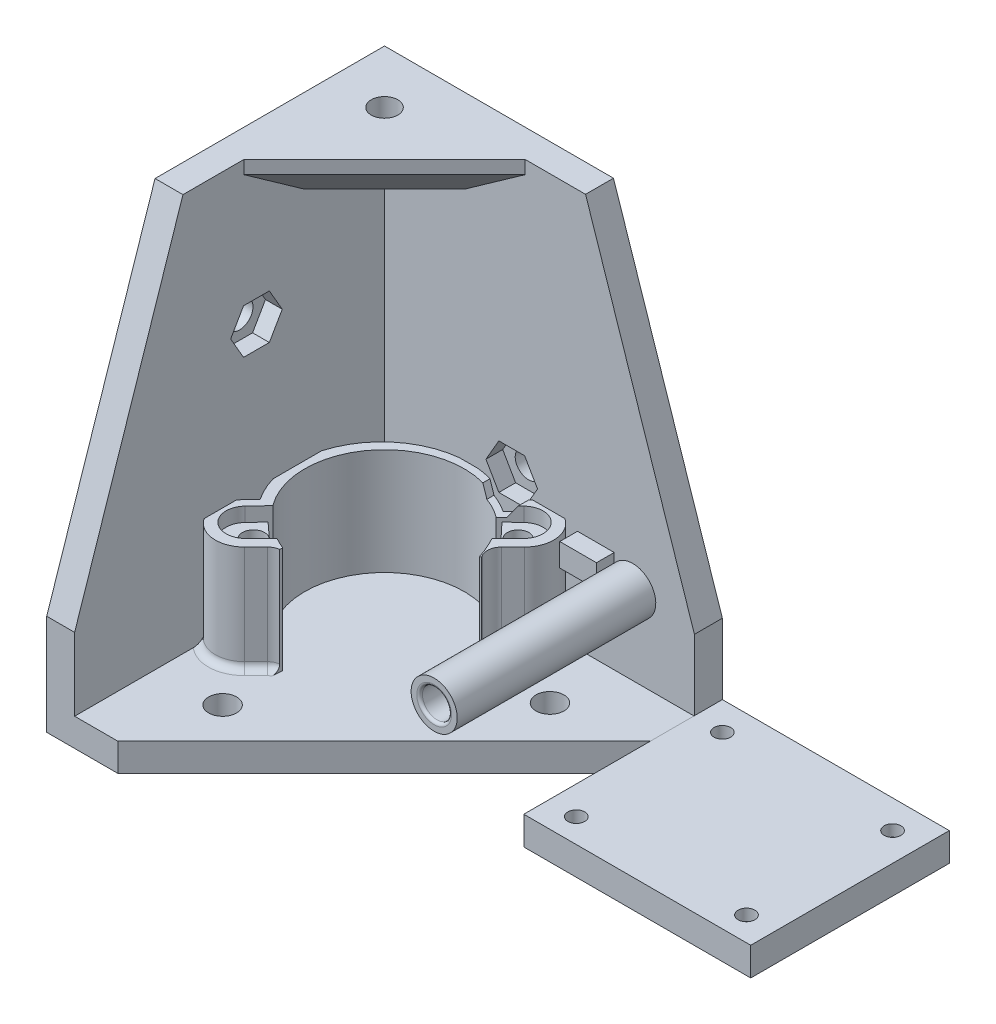
SolidWorks part; units mm, degrees
ref_plane "Front" through (0, 0, 0) normal (0, 0, 1) x (1, 0, 0)
ref_plane "Top" through (0, 0, 0) normal (0, 1, 0) x (1, 0, 0)
ref_plane "Right" through (0, 0, 0) normal (1, 0, 0) x (0, 0, -1)
sketch "Sketch1" plane through (0, 0, 0) normal (0, 1, 0) x (1, 0, 0)
  line L0 (0, 0) -> (0, 60.5)
  line L1 (0, -55) -> (0, 55) construction
  line L2 (0, 60.5) -> (60.5, 60.5)
  line L3 (60.5, 60.5) -> (60.5, 47.75)
  line L4 (60.5, 47.75) -> (12.75, 0)
  line L5 (-55, 0) -> (55, 0) construction
  line L6 (12.75, 0) -> (0, 0)
  dimension "D1" = 60.5
  dimension "D2" = 12.75
extrude "Boss-Extrude1" add sketch "Sketch1" along normal blind 5
sketch "Sketch4" plane through (0, 0, 0) normal (-1, 0, 0) x (0, 0, 1)
  line L0 (-60.5, 5) -> (-60.5, 76.1962)
  line L1 (-60.5, 76.1962) -> (-19.4, 76.1962)
  line L2 (-19.4, 76.1962) -> (0, 18.0048)
  line L3 (0, 18.0048) -> (0, 5)
  line L4 (0, -37.675) -> (0, 37.675) construction
  line L5 (-60.5, 5) -> (0, 5) construction
  line L6 (-60.5, 5) -> (0, 5)
  dimension "D1" = 71.1962
  dimension "D2" = 41.1
  dimension "D3" = 61.34
extrude "Boss-Extrude2" add sketch "Sketch4" against normal blind 5
sketch "Sketch5" plane through (0, 0, -60.5) normal (0, 0, -1) x (-1, 0, 0)
  line L0 (0, 76.1962) -> (-41, 76.1962)
  line L1 (-41, 76.1962) -> (-60.5, 17.7009)
  line L2 (-60.5, 17.7009) -> (-60.5, 5)
  line L6 (-60.5, 0) -> (0, 0)
  line L7 (0, 0) -> (0, 76.1962)
  line L8 (0, 76.1962) -> (-5, 76.1962)
  line L9 (-5, 76.1962) -> (-5, 5)
  line L10 (-5, 5) -> (-60.5, 5)
  line L11 (-60.5, 5) -> (-60.5, 0)
  line L12 (-60.5, 0) -> (0, 0)
  line L13 (0, 0) -> (0, 76.1962)
  line L14 (0, 76.1962) -> (-5, 76.1962)
  line L15 (-5, 76.1962) -> (-5, 5)
  line L16 (-5, 5) -> (-60.5, 5)
  line L17 (-60.5, 5) -> (-60.5, 0)
  line M13 (-5, 76.1962) -> (-5, 5)
  line M14 (-5, 5) -> (-60.5, 5)
  dimension "D2" = 41
  dimension "D3" = 61.66
  dimension "D1" = 0
extrude "Boss-Extrude3" add sketch "Sketch5" against normal blind 5 contours L1 L2 L0 M14 M13 region at (29.1655, 37.8824, -60.5)
sketch "Sketch6" plane through (0, 5, 0) normal (0, 1, 0) x (1, 0, 0)
  line L0 (60.5, 60.5) -> (0, 60.5) construction
  line L4 (0, 19.4) -> (0, 0)
  line L5 (60.5, 55.5) -> (5, 55.5)
  line L6 (5, 55.5) -> (5, 0)
  line L7 (5, 0) -> (12.75, 0)
  line L8 (12.75, 0) -> (60.5, 47.75)
  line L9 (60.5, 47.75) -> (60.5, 55.5)
  line L10 (60.5, 55.5) -> (5, 55.5)
  line L11 (5, 55.5) -> (5, 0)
  line L12 (5, 0) -> (12.75, 0)
  line L13 (12.75, 0) -> (60.5, 47.75)
  line L14 (60.5, 47.75) -> (60.5, 55.5)
  line L15 (0, 0) -> (5, 0)
  line L16 (5, 0) -> (5, 19.4)
  line L17 (5, 19.4) -> (0, 19.4)
  line L18 (0, 19.4) -> (0, 0)
  line L19 (0, 0) -> (5, 0)
  line L20 (5, 0) -> (5, 19.4)
  line L21 (5, 19.4) -> (0, 19.4)
  line L24 (0, 60.5) -> (0, 19.4)
  line L25 (0, 19.4) -> (5, 19.4)
  line L26 (5, 19.4) -> (5, 55.5)
  line L27 (5, 55.5) -> (41, 55.5)
  line L28 (41, 55.5) -> (41, 60.5)
  line L29 (41, 60.5) -> (0, 60.5)
  line L30 (0, 60.5) -> (0, 19.4)
  line L31 (0, 19.4) -> (5, 19.4)
  line L32 (5, 19.4) -> (5, 55.5)
  line L33 (5, 55.5) -> (41, 55.5)
  line L34 (41, 55.5) -> (41, 60.5)
  line L35 (41, 60.5) -> (0, 60.5)
  circle A0 centre (16.5, 15) radius 2.5
  circle A1 centre (45.5, 44.625) radius 2.5
  dimension "D1" = 5
  dimension "D2" = 5
  dimension "D3" = 0
  dimension "D4" = 15
  dimension "D6" = 16.5
  dimension "D7" = 15
  dimension "D9" = 15.875
  dimension "D5" = 0
  dimension "D8" = 0
extrude "Cut-Extrude1" cut sketch "Sketch6" against normal through all contours A0 | A1 region at (16.5, 5, -15) region at (45.5, 5, -44.625)
sketch "Sketch9" plane through (0, 0, -55.5) normal (0, 0, 1) x (1, 0, 0)
  line L1 (5, 76.1962) -> (5, 5) construction
  line L5 (0, 0) -> (60.5, 0)
  line L6 (0, 76.1962) -> (0, 0)
  line L7 (41, 76.1962) -> (0, 76.1962)
  line L8 (60.5, 17.7009) -> (41, 76.1962)
  line L9 (60.5, 0) -> (60.5, 17.7009)
  line L10 (0, 0) -> (60.5, 0)
  line L11 (0, 76.1962) -> (0, 0)
  line L12 (41, 76.1962) -> (0, 76.1962)
  line L13 (60.5, 17.7009) -> (41, 76.1962)
  line L14 (60.5, 0) -> (60.5, 17.7009)
  line L15 (49.45, 19.0462) -> (49.45, 3.6199) construction
  circle A0 centre (49.45, 19.0462) radius 4.1275
  circle A1 centre (49.45, 19.0462) radius 2.6035
  dimension "D2" = 5.207
  dimension "D3" = 1.524
  dimension "D4" = 57.15
  dimension "D5" = 44.45
  dimension "D1" = 0
extrude "Boss-Extrude5" add sketch "Sketch9" along normal blind 35.56 contours A1 A0 region at (45.4392, 19.0462, -55.5)
fillet "Fillet1" radius 0.508 1 edges at (52.0535, 19.0462, -19.94)
sketch "Sketch14" plane through (0, 5, 0) normal (0, 1, 0) x (1, 0, 0)
  line L0 (13.4627, 27.5396) -> (14.7681, 26.7924)
  line L1 (12.75, 0) -> (60.5, 47.75) construction
  line L2 (36.625, 23.875) -> (5, 55.5) construction
  line L3 (5, 55.5) -> (60.5, 55.5) construction
  line L4 (32.9604, 47.0373) -> (33.7076, 45.7319)
  line L5 (14.8281, 26.8523) -> (11.8274, 23.8516)
  line L6 (6.723, 28.8027) -> (9.1327, 31.3641)
  line L7 (33.6477, 45.6719) -> (36.6484, 48.6726)
  line L8 (31.6973, 53.777) -> (29.1359, 51.3673)
  line L9 (15.0744, 24.4582) -> (13.006, 22.3898)
  line L10 (5.6561, 29.7396) -> (7.0609, 31.1444)
  line L11 (36.0418, 45.4256) -> (38.1102, 47.494)
  line L12 (30.7604, 54.8439) -> (28.83, 52.9135)
  line L13 (18.1324, 24.8665) -> (30.5234, 17.7734)
  line L14 (35.6335, 42.3676) -> (42.7266, 29.9766)
  line L15 (31.7409, 18.9909) -> (18.852, 25.7543)
  line L16 (41.5091, 28.7591) -> (34.7457, 41.648)
  line L17 (16.5689, 25.6946) -> (16.5343, 25.1798)
  line L18 (34.7457, 41.648) -> (35.7996, 42.0774)
  circle A0 centre (20.5607, 39.9393) radius 14.2875
  arc A1 (11.8274, 23.8516) -> (6.723, 28.8027) centre (9.3129, 26.3661) cw
  arc A2 (36.6484, 48.6726) -> (31.6973, 53.777) centre (34.1339, 51.1871) ccw
  arc A3 (13.006, 22.3898) -> (5.6561, 29.7396) centre (9.3311, 26.0647) cw
  arc A4 (38.1102, 47.494) -> (30.7604, 54.8439) centre (34.4353, 51.1689) ccw
  arc A5 (7.0609, 31.1444) -> (28.83, 52.9135) centre (20.0709, 39.9035) cw
  arc A6 (36.0418, 45.4256) -> (35.6335, 42.3676) centre (37.8378, 43.6295) ccw
  arc A7 (15.0744, 24.4582) -> (18.1324, 24.8665) centre (16.8705, 22.6622) cw
  arc A9 (33.8602, 45.8844) -> (36.3595, 38.5726) centre (13.6025, 34.877) cw
  arc A10 (14.6156, 26.6398) -> (21.9274, 24.1405) centre (25.623, 46.8975) ccw
  point P40 (34.6689, 44.0527)
  point P43 (16.4473, 25.8311)
  line M13 (60.5, 55.5) -> (5, 55.5)
  line M14 (5, 55.5) -> (5, 0)
  line M16 (12.75, 0) -> (60.5, 47.75)
  dimension "D1" = 28.575
  dimension "D2" = 3.556
  dimension "D3" = 2.54
extrude "Boss-Extrude6" add sketch "Sketch14" along normal blind 19.05 contours L2 A0 L5 A1 L6 A5 L10 A3 L9 A7 L13 M16 M14 | L2 L14 A6 L11 A4 L12 A5 A0 L8 A2 L7 M16 M13 region at (7.691, 5, -30.3062) region at (10.0875, 5, -50.8829)
sketch "Sketch15" plane through (0, 76.1962, 0) normal (0, 1, 0) x (1, 0, 0)
  line L0 (5, 30.3375) -> (30.1625, 55.5)
  line L1 (0, -33.275) -> (0, 33.275) construction
  line L2 (41, 60.5) -> (0, 60.5) construction
  line L6 (0, 60.5) -> (0, 19.4)
  line L7 (0, 19.4) -> (5, 19.4)
  line L8 (5, 19.4) -> (5, 55.5)
  line L9 (5, 55.5) -> (41, 55.5)
  line L10 (41, 55.5) -> (41, 60.5)
  line L11 (41, 60.5) -> (0, 60.5)
  line L13 (0, 19.4) -> (5, 19.4)
  line L14 (5, 30.3375) -> (5, 55.5)
  line L15 (5, 55.5) -> (30.1625, 55.5)
  line L16 (41, 55.5) -> (41, 60.5)
  circle A0 centre (9.525, 50.975) radius 2.3812
  line M11 (5, 19.4) -> (5, 55.5)
  line M12 (5, 55.5) -> (41, 55.5)
  dimension "D3" = 4.7625
  dimension "D4" = 9.525
  dimension "D5" = 9.525
  dimension "D2" = 45
  dimension "D1" = 0
extrude "Boss-Extrude7" add sketch "Sketch15" against normal blind 10 contours L0 A0 M11 M12 region at (13.6178, 76.1962, -46.8822)
chamfer "Chamfer2" distance 7.62 angle 45 1 edges at (17.5813, 66.1962, -42.9187)
fillet "Fillet2" radius 1.27 7 edges at (39.6065, 5, -51.6871) (37.076, 5, -46.4598) (35.3202, 5, -43.9657) (8.8129, 5, -20.8935) (14.0402, 5, -23.424) (15.745, 5, -24.9392) (35.7165, 5, -42.2225)
sketch "Sketch16" plane through (0, 0, -55.5) normal (0, 0, 1) x (1, 0, 0)
  line L1 (46.1305, 23.2107) -> (38.2864, 23.2107)
  line L2 (46.1305, 23.2107) -> (46.1305, 19.0978)
  line L3 (46.1305, 19.0978) -> (38.2864, 19.0978)
  line L4 (38.2864, 23.2107) -> (38.2864, 19.0978)
extrude "Boss-Extrude8" add sketch "Sketch16" along normal blind 3.175
chamfer "Chamfer3" distance 1.27 angle 45 1 edges at (38.2864, 23.2107, -55.0794)
sketch "Sketch17" plane through (0, 5, 0) normal (0, 1, 0) x (1, 0, 0)
  line L0 (8.716, 30.9212) -> (14.047, 26.0712)
  line L1 (36.625, 23.875) -> (5, 55.5) construction
  line L2 (12.75, 0) -> (60.5, 47.75) construction
  line L3 (5, 55.5) -> (18.418, 55.5) construction
  line L4 (5, 55.5) -> (5, 44.2452) construction
  line L5 (29.6632, 51.8634) -> (34.5959, 46.6202)
  line L22 (37.3079, 55.5) -> (31.5627, 55.5)
  line L23 (30.7604, 54.8439) -> (28.83, 52.9135)
  line L24 (21.7238, 55.5) -> (18.418, 55.5)
  line L25 (5, 44.2452) -> (5, 35.5618)
  line L26 (7.0609, 31.1444) -> (5.6561, 29.7396)
  line L27 (5, 28.9373) -> (5, 23.1921)
  line L28 (13.006, 22.3898) -> (15.0744, 24.4582)
  line L29 (16.5343, 25.1798) -> (16.5689, 25.6946)
  line L30 (16.5343, 25.1798) -> (16.5689, 25.6946)
  line L31 (35.539, 41.9712) -> (35.7996, 42.0774)
  line L32 (35.539, 41.9712) -> (35.7996, 42.0774)
  line L33 (14.6156, 26.6398) -> (11.8274, 23.8516)
  line L34 (6.723, 28.8027) -> (9.1327, 31.3641)
  line L35 (29.1359, 51.3673) -> (31.6973, 53.777)
  line L36 (36.6484, 48.6726) -> (33.8602, 45.8844)
  line L40 (35.7996, 42.0774) -> (35.6335, 42.3676)
  line L41 (36.0418, 45.4256) -> (38.1102, 47.494)
  line L43 (37.3079, 55.5) -> (31.5627, 55.5)
  line L44 (30.7604, 54.8439) -> (28.83, 52.9135)
  line L45 (21.7238, 55.5) -> (18.418, 55.5)
  line L46 (5, 44.2452) -> (5, 35.5618)
  line L47 (7.0609, 31.1444) -> (5.6561, 29.7396)
  line L48 (5, 28.9373) -> (5, 23.1921)
  line L49 (13.006, 22.3898) -> (15.0744, 24.4582)
  line L54 (14.6156, 26.6398) -> (11.8274, 23.8516)
  line L55 (6.723, 28.8027) -> (9.1327, 31.3641)
  line L56 (29.1359, 51.3673) -> (31.6973, 53.777)
  line L57 (36.6484, 48.6726) -> (33.8602, 45.8844)
  line L61 (35.7996, 42.0774) -> (35.6335, 42.3676)
  line L62 (36.0418, 45.4256) -> (38.1102, 47.494)
  circle A1 centre (33.6908, 50.7324) radius 2.1828
  circle A2 centre (10.0204, 27.0078) radius 1.9844
  circle A3 centre (33.6908, 50.7324) radius 1.9288
  arc A15 (38.1102, 47.494) -> (37.3079, 55.5) centre (34.4353, 51.1689) ccw
  arc A17 (31.5627, 55.5) -> (30.7604, 54.8439) centre (34.4353, 51.1689) ccw
  arc A18 (28.83, 52.9135) -> (21.7238, 55.5) centre (20.0709, 39.9035) ccw
  arc A19 (18.418, 55.5) -> (5, 44.2452) centre (20.0709, 39.9035) ccw
  arc A20 (5, 35.5618) -> (7.0609, 31.1444) centre (20.0709, 39.9035) ccw
  arc A21 (5.6561, 29.7396) -> (5, 28.9373) centre (9.3311, 26.0647) ccw
  arc A22 (5, 23.1921) -> (13.006, 22.3898) centre (9.3311, 26.0647) ccw
  arc A23 (16.5343, 25.1798) -> (15.0744, 24.4582) centre (16.8705, 22.6622) ccw
  arc A24 (14.6156, 26.6398) -> (16.5689, 25.6946) centre (25.623, 46.8975) ccw
  arc A25 (6.723, 28.8027) -> (11.8274, 23.8516) centre (9.3129, 26.3661) ccw
  arc A26 (29.1359, 51.3673) -> (9.1327, 31.3641) centre (20.5607, 39.9393) ccw
  arc A27 (36.6484, 48.6726) -> (31.6973, 53.777) centre (34.1339, 51.1871) ccw
  arc A28 (35.539, 41.9712) -> (33.8602, 45.8844) centre (13.6025, 34.877) ccw
  arc A29 (36.0418, 45.4256) -> (35.6335, 42.3676) centre (37.8378, 43.6295) ccw
  arc A30 (38.1102, 47.494) -> (37.3079, 55.5) centre (34.4353, 51.1689) ccw
  arc A32 (31.5627, 55.5) -> (30.7604, 54.8439) centre (34.4353, 51.1689) ccw
  arc A33 (28.83, 52.9135) -> (21.7238, 55.5) centre (20.0709, 39.9035) ccw
  arc A34 (18.418, 55.5) -> (5, 44.2452) centre (20.0709, 39.9035) ccw
  arc A35 (5, 35.5618) -> (7.0609, 31.1444) centre (20.0709, 39.9035) ccw
  arc A36 (5.6561, 29.7396) -> (5, 28.9373) centre (9.3311, 26.0647) ccw
  arc A37 (5, 23.1921) -> (13.006, 22.3898) centre (9.3311, 26.0647) ccw
  arc A38 (16.5343, 25.1798) -> (15.0744, 24.4582) centre (16.8705, 22.6622) ccw
  arc A39 (14.6156, 26.6398) -> (16.5689, 25.6946) centre (25.623, 46.8975) ccw
  arc A40 (6.723, 28.8027) -> (11.8274, 23.8516) centre (9.3129, 26.3661) ccw
  arc A41 (29.1359, 51.3673) -> (9.1327, 31.3641) centre (20.5607, 39.9393) ccw
  arc A42 (36.6484, 48.6726) -> (31.6973, 53.777) centre (34.1339, 51.1871) ccw
  arc A43 (35.539, 41.9712) -> (33.8602, 45.8844) centre (13.6025, 34.877) ccw
  arc A44 (36.0418, 45.4256) -> (35.6335, 42.3676) centre (37.8378, 43.6295) ccw
  line M44 (33.8602, 45.8844) -> (36.6484, 48.6726)
  arc M45 (36.6484, 48.6726) -> (31.6973, 53.777) centre (34.1339, 51.1871) ccw
  line M46 (31.6973, 53.777) -> (29.1359, 51.3673)
  line M48 (9.1327, 31.3641) -> (6.723, 28.8027)
  arc M49 (6.723, 28.8027) -> (11.8274, 23.8516) centre (9.3129, 26.3661) ccw
  line M50 (11.8274, 23.8516) -> (14.6156, 26.6398)
  dimension "D2" = 3.9688
  dimension "D3" = 0.254
  dimension "D1" = 0
extrude "Boss-Extrude9" add sketch "Sketch17" along normal offset from surface (16.51 mm away) 2.54 contours L5 A1 M46 M44 M45 | L0 M48 M49 M50 | A1 L5 A3 region at (11.3737, 5, -28.4876) region at (30.7585, 5, -52.737) region at (33.0584, 5, -52.7569) up to face at (20.9693, 24.05, -39.9839)
sketch "Sketch18" plane through (0, 0, 0) normal (-1, 0, 0) x (0, 0, 1)
  line L0 (-60.5, 76.1962) -> (-60.5, 0) construction
  line L1 (33.275, 0) -> (-33.275, 0) construction
  circle A0 centre (-32.56, 49.53) radius 2.3813
  dimension "D1" = 27.94
  dimension "D2" = 49.53
  dimension "D3" = 4.7625
extrude "Cut-Extrude2" cut sketch "Sketch18" against normal up to next
sketch "Sketch19" plane through (0, 0, -60.5) normal (0, 0, -1) x (-1, 0, 0)
  line L0 (0, 33.275) -> (0, -33.275) construction
  line L1 (33.275, 0) -> (-33.275, 0) construction
  circle A0 centre (-27.7812, 26.1937) radius 2.3813
  dimension "D1" = 27.7812
  dimension "D2" = 26.1937
  dimension "D3" = 4.7625
extrude "Cut-Extrude3" cut sketch "Sketch19" against normal up to next
sketch "Sketch20" plane through (0, 0, -55.5) normal (0, 0, 1) x (1, 0, 0)
  line L1 (32.4001, 26.1938) -> (30.0907, 30.1938)
  line L2 (30.0907, 30.1938) -> (25.4718, 30.1938)
  line L3 (25.4718, 30.1938) -> (23.1624, 26.1938)
  line L4 (23.1624, 26.1938) -> (25.4718, 22.1938)
  line L5 (25.4718, 22.1938) -> (30.0907, 22.1938)
  line L6 (30.0907, 22.1938) -> (32.4001, 26.1938)
  circle A0 centre (27.7812, 26.1937) radius 2.3813 construction
  circle A1 centre (27.7812, 26.1937) radius 2.3813
  circle A2 centre (27.7812, 26.1937) radius 4 construction
  dimension "D1" = 8
extrude "Cut-Extrude4" cut sketch "Sketch20" against normal blind 3 and the other way up to vertex (4.1327 mm away) contours L1 L2 L3 L4 L5 L6 other way up to point (29.1359, 24.05, -51.3673)
sketch "Sketch21" plane through (5, 0, 0) normal (1, 0, 0) x (0, 0, -1)
  line L1 (34.8694, 53.53) -> (30.2506, 53.53)
  line L2 (30.2506, 53.53) -> (27.9412, 49.53)
  line L3 (27.9412, 49.53) -> (30.2506, 45.53)
  line L4 (30.2506, 45.53) -> (34.8694, 45.53)
  line L5 (34.8694, 45.53) -> (37.1788, 49.53)
  line L6 (37.1788, 49.53) -> (34.8694, 53.53)
  circle A0 centre (32.56, 49.53) radius 2.3813 construction
  circle A1 centre (32.56, 49.53) radius 2.3812
  circle A2 centre (32.56, 49.53) radius 4 construction
  dimension "D1" = 8
extrude "Cut-Extrude5" cut sketch "Sketch21" against normal blind 3 contours L1 L2 L3 L4 L5 L6
sketch "Sketch23" plane through (0, 0, 0) normal (0, 1, 0) x (1, 0, 0)
  line L1 (60.5, 60.5) -> (101.14, 60.5)
  line L2 (60.5, 60.5) -> (60.5, 24.94)
  line L3 (60.5, 24.94) -> (101.14, 24.94)
  line L4 (101.14, 60.5) -> (101.14, 24.94)
  dimension "D1" = 40.64
  dimension "D2" = 35.56
extrude "Boss-Extrude12" add sketch "Sketch23" along normal blind 5.08
sketch "Sketch24" plane through (0, 5.08, 0) normal (0, 1, 0) x (1, 0, 0)
  line L0 (101.14, 60.5) -> (60.5, 60.5) construction
  line L1 (60.5, 47.75) -> (60.5, 55.5) construction
  circle A0 centre (65.58, 55.42) radius 1.5
  circle A1 centre (96.06, 55.42) radius 1.5
  circle A2 centre (96.06, 29.258) radius 1.5
  circle A3 centre (65.58, 29.258) radius 1.5
  dimension "D1" = 3
  dimension "D2" = 26.162
  dimension "D3" = 30.48
  dimension "D4" = 5.08
  dimension "D5" = 5.08
extrude "Cut-Extrude6" cut sketch "Sketch24" against normal up to next
sketch "Sketch25" plane through (0, 0, 0) normal (0, -1, 0) x (1, 0, 0)
  line L1 (67.2399, -32.133) -> (68.8998, -29.258)
  line L2 (68.8998, -29.258) -> (67.2399, -26.383)
  line L3 (67.2399, -26.383) -> (63.9201, -26.383)
  line L4 (63.9201, -26.383) -> (62.2602, -29.258)
  line L5 (62.2602, -29.258) -> (63.9201, -32.133)
  line L6 (63.9201, -32.133) -> (67.2399, -32.133)
  line L7 (94.4001, -32.133) -> (97.7199, -32.133)
  line L8 (97.7199, -32.133) -> (99.3798, -29.258)
  line L9 (99.3798, -29.258) -> (97.7199, -26.383)
  line L10 (97.7199, -26.383) -> (94.4001, -26.383)
  line L11 (94.4001, -26.383) -> (92.7402, -29.258)
  line L12 (92.7402, -29.258) -> (94.4001, -32.133)
  line L13 (92.7402, -55.42) -> (94.4001, -58.295)
  line L14 (94.4001, -58.295) -> (97.7199, -58.295)
  line L15 (97.7199, -58.295) -> (99.3798, -55.42)
  line L16 (99.3798, -55.42) -> (97.7199, -52.545)
  line L17 (97.7199, -52.545) -> (94.4001, -52.545)
  line L18 (94.4001, -52.545) -> (92.7402, -55.42)
  line L19 (68.8998, -55.42) -> (67.2399, -52.545)
  line L20 (67.2399, -52.545) -> (63.9201, -52.545)
  line L21 (63.9201, -52.545) -> (62.2602, -55.42)
  line L22 (62.2602, -55.42) -> (63.9201, -58.295)
  line L23 (63.9201, -58.295) -> (67.2399, -58.295)
  line L24 (67.2399, -58.295) -> (68.8998, -55.42)
  circle A0 centre (65.58, -29.258) radius 1.5 construction
  circle A1 centre (65.58, -29.258) radius 1.5
  circle A2 centre (96.06, -29.258) radius 1.5 construction
  circle A3 centre (96.06, -29.258) radius 1.5
  circle A4 centre (65.58, -55.42) radius 1.5 construction
  circle A5 centre (65.58, -55.42) radius 1.5
  circle A6 centre (96.06, -55.42) radius 1.5 construction
  circle A7 centre (96.06, -55.42) radius 1.5
  circle A8 centre (65.58, -29.258) radius 2.875 construction
  circle A9 centre (96.06, -29.258) radius 2.875 construction
  circle A10 centre (96.06, -55.42) radius 2.875 construction
  circle A11 centre (65.58, -55.42) radius 2.875 construction
  dimension "D1" = 5.75
  dimension "D2" = 5.75
  dimension "D3" = 5.75
  dimension "D4" = 5.75
extrude "Cut-Extrude7" cut sketch "Sketch25" against normal blind 3
sketch "Sketch26" plane through (0, 66.1962, 0) normal (0, -1, 0) x (1, 0, 0)
  line L1 (13.0753, -53.024) -> (13.0747, -48.9248)
  line L2 (13.0747, -48.9248) -> (9.5243, -46.8758)
  line L3 (9.5243, -46.8758) -> (5.9747, -48.926)
  line L4 (5.9747, -48.926) -> (5.9753, -53.0252)
  line L5 (5.9753, -53.0252) -> (9.5257, -55.0742)
  line L6 (9.5257, -55.0742) -> (13.0753, -53.024)
  circle A0 centre (9.525, -50.975) radius 2.3813 construction
  circle A1 centre (9.525, -50.975) radius 2.3813
  circle A2 centre (9.525, -50.975) radius 3.55 construction
  point P3 (13.0747, -53.0252)
  dimension "D1" = 7.1
extrude "Cut-Extrude8" cut sketch "Sketch26" against normal blind 3.5
